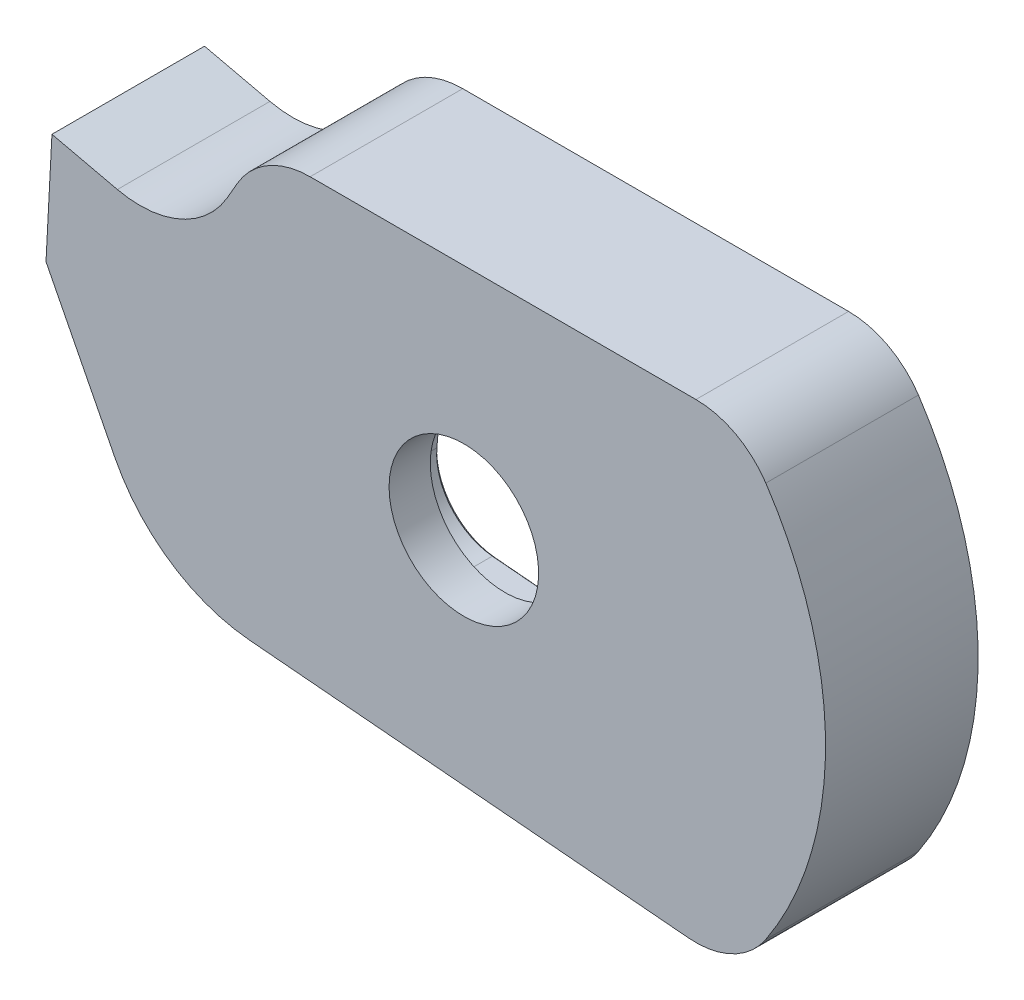
SolidWorks part; units mm, degrees
material "AISI 4340 Aço, normalizado"
ref_plane "Plano frontal" through (0, 0, 0) normal (0, 0, 1) x (1, 0, 0)
ref_plane "Plano superior" through (0, 0, 0) normal (0, 1, 0) x (1, 0, 0)
ref_plane "Plano direito" through (0, 0, 0) normal (1, 0, 0) x (0, 0, -1)
other "Center of Mass"
sketch "Sketch2" plane through (0, 0, 0) normal (0, 0, 1) x (1, 0, 0)
  line L0 (0, 0) -> (-50, 0) construction
  line L1 (-115.1603, 41.8011) -> (-136.5964, 46.75)
  line L2 (0, 0) -> (-142.97, 20.0931) construction
  line L5 (-51.9968, 77) -> (74.4153, 77)
  line L6 (0, 0) -> (0, 41.2714) construction
  line L8 (-75.8125, 63.25) -> (-79.158, 57.4553)
  line L14 (-71.7951, -64.424) -> (71.9488, -77)
  line L19 (-136.5964, 46.75) -> (-138.542, 9.625)
  line L20 (-137.1069, 44.5388) -> (-135.4014, 51.9262) construction
  line L22 (-138.542, 9.625) -> (-116.0069, -34.6028)
  circle A0 centre (0, 0) radius 144.375 construction
  arc A5 (74.4153, 77) -> (97.3123, 64.7308) centre (74.4153, 49.5) cw
  arc A6 (-51.9968, 77) -> (-75.8125, 63.25) centre (-51.9968, 49.5) ccw
  arc A17 (-116.0069, -34.6028) -> (-71.7951, -64.424) centre (-67.0015, -9.6333) ccw
  arc A18 (-115.1603, 41.8011) -> (-79.158, 57.4553) centre (-107.7369, 73.9553) ccw
  arc A20 (97.3123, 64.7308) -> (97.2212, -64.8676) centre (0, 0) cw
  arc A21 (71.9488, -77) -> (97.2212, -64.8676) centre (74.3456, -49.6046) ccw
  point P29 (-144.375, 0)
  point P31 (29.3939, 77)
  point P32 (-67.8739, 77)
  point P33 (97.3123, -64.7308)
  dimension "D1" = 288.75
  dimension "D4" = 27.5
  dimension "D5" = 33
  dimension "D13" = 27.5
  dimension "D11" = 55
  dimension "D10" = 77
  dimension "D2" = 5
  dimension "D3" = 10
  dimension "D7" = 30
  dimension "D8" = 77
  dimension "D12" = 30
  dimension "D9" = 46.75
  dimension "D14" = 37.125
  dimension "D15" = 22
  dimension "D6" = 27.5
  dimension "D16" = 5
  dimension "D17" = 77
extrude "EXTRUSÃO GEOMETRIA" add sketch "Sketch2" along normal blind 50 contours L5 A5 A20 A21 L14 A17 L22 L19 L1 A18 L8 A6
sketch "Esboço3"
  line L0 (119.5605, -25.8367) -> (117.6529, -4.0323)
  line L1 (125.3653, 6.5829) -> (138.542, 9.625)
  line L2 (138.542, 9.625) -> (116.0069, -34.6028) construction
  line L3 (138.542, 9.625) -> (116.0069, -34.6028)
  line L4 (71.7951, -64.424) -> (-71.9488, -77) construction
  line L5 (115.1603, 41.8011) -> (136.5964, 46.75) construction
  line L6 (31.1551, 77) -> (-22.8799, 20.2266)
  line L7 (51.9968, 77) -> (-74.4153, 77) construction
  line L8 (-28.0452, 17.3392) -> (-116.865, -1.5321)
  line L9 (31.1551, 77) -> (-74.4153, 77)
  arc A0 (71.7951, -64.424) -> (116.0069, -34.6028) centre (67.0015, -9.6333) ccw construction
  arc A1 (117.6529, -4.0323) -> (125.3653, 6.5829) centre (127.6148, -3.1608) cw
  arc A2 (119.5605, -25.8367) -> (116.0069, -34.6028) centre (67.0015, -9.6333) ccw
  arc A3 (-97.3123, 64.7308) -> (-97.2212, -64.8676) centre (0, 0) ccw construction
  arc A4 (-22.8799, 20.2266) -> (-28.0452, 17.3392) centre (-30.1235, 27.1209) cw
  arc A5 (-74.4153, 77) -> (-97.3123, 64.7308) centre (-74.4153, 49.5) ccw construction
  arc A6 (-97.3123, 64.7308) -> (-116.865, -1.5321) centre (0, 0) ccw
  arc A7 (-74.4153, 77) -> (-97.3123, 64.7308) centre (-74.4153, 49.5) ccw
  point P11 (-22.8799, 20.2266)
  point P24 (-36.8917, 15.4596)
  dimension "D1" = 10
  dimension "D3" = 10
  dimension "D2" = 22
sketch "Esboço3<3>" plane through (0, 0, 0) normal (0, 0, -1) x (-1, 0, 0) same geometry as "Esboço3"
other "Ponto de referência do centro da massa1"
ref_plane "Plano2" through (0, 1.9378, 0) normal (0, -1, 0) x (-1, 0, 0)
ref_plane "Plano3" through (-1.6368, 0, 0) normal (1, 0, 0) x (0, 0, -1)
sketch "Esboço2" plane through (0, 0, 0) normal (0, 0, -1) x (-1, 0, 0)
  line L0 (-8.25, 1.9378) -> (8.25, 1.9378) construction
  line L1 (-38.0236, 53.678) -> (31.7101, 59.7789)
  line L2 (-56.2044, 32.011) -> (-50.1035, -37.7226)
  line L3 (-28.4364, -55.9034) -> (41.2972, -49.8025)
  line L4 (53.3771, 41.5982) -> (59.478, -28.1355)
  line L5 (-57.9475, 51.9349) -> (61.2211, -48.0594) construction
  line L6 (-48.3603, -57.6465) -> (51.6339, 61.5221) construction
  line L7 (1.6368, 8.25) -> (1.6368, -8.25) construction
  line L8 (71.7951, -64.424) -> (-71.9488, -77) construction
  line L10 (2.503, 1.9378) -> (86.0271, 1.9378) construction
  circle A0 centre (1.6368, 1.9378) radius 24.5
  arc A2 (-38.0236, 53.678) -> (-56.2044, 32.011) centre (-36.2805, 33.7542) ccw
  arc A3 (31.7101, 59.7789) -> (53.3771, 41.5982) centre (33.4532, 39.8551) cw
  arc A4 (41.2972, -49.8025) -> (59.478, -28.1355) centre (39.5541, -29.8786) ccw
  arc A5 (-50.1035, -37.7226) -> (-28.4364, -55.9034) centre (-30.1796, -35.9795) ccw
  circle A6 centre (1.6368, 1.9378) radius 42.5
  dimension "D1" = 20
  dimension "D2" = 49
  dimension "D5" = 85
  dimension "D3" = 110
  dimension "D4" = 110
extrude "REBAIXO CAMISA" cut sketch "Esboço2" against normal blind 36.5 contours L1 A3 L4 A4 L3 A5 L2 A2
extrude "FURO EIXO" cut sketch "Esboço2<3>" against normal through all contours A0
sketch "Esboço2<3>" plane through (0, 0, 0) normal (0, 0, -1) x (-1, 0, 0) same geometry as "Esboço2"
chamfer "CHANFRO CAMISA" distance 1 angle 45 8 edges at (-6.4304, -52.8529, 0) (43.0353, -51.3004, 0) (-54.875, -42.7343, 0) (53.1539, -2.8558, 0) (-56.4275, 6.7314, 0) (51.6013, 46.6099, 0) (-46.3089, 55.1759, 0) (3.1568, 56.7285, 0)
sketch "REF. POLIA" plane through (0, 0, 0) normal (0, 0, -1) x (-1, 0, 0)
  circle A0 centre (1.6368, 1.9378) radius 75
  circle A1 centre (1.6368, 1.9378) radius 24.5 construction
  point P5 (0, 0)
  point P6 (10.688, 17.267)
  dimension "D1" = 150
equation "\"escala\" = 1                                            'projeto - escala geral"
equation "\"escala_disco-arma\"= 2.75                               'disco arma - escala geometria disco arma"
equation "\"rolamento_D-ext\"= 85                                   'rolamento arma - diametro externo"
equation "\"rolamento_d-int\"= 45                                   'rolamento arma - diametro interno"
equation "\"rolamento_b-esp\"= 23                                   'rolamento arma - espessura"
equation "\"arma_rebaixo-camisa_b\"= \"rolamento_b-esp\" + (\"arma-espessura\"-\"rolamento_b-esp\")/2        'disco arma - profundidade rebaixo camisa"
equation "\"arma-espessura\"= 50                                    'disco arma - espessura disco arma"
equation "\"D1@EXTRUSÃO GEOMETRIA\" = \"arma-espessura\""
equation "\"eixo_diam\"= \"rolamento_d-int\"                          'eixo arma - diametro"
equation "\"D2@Esboço2\" = \"eixo_diam\" + \"arma_eixo-furo_folga\""
equation "\"camisa_largura\"=110                                    'camisa arma - tamanho do lado"
equation "\"D3@Esboço2\"=\"camisa_largura\""
equation "\"camisa_raio\"=15                                        'camisa arma - raio canto interno"
equation "\"arma_rebaixo-camisa_raio\" = 5 + \"camisa_raio\"          'raio do rebaixo da camisa da arma "
equation "\"D1@Esboço2\"=\"arma_rebaixo-camisa_raio\""
equation "\"arma_alivio_raio\" = 12 * \"escala_disco-arma\""
equation "\"arma_diam_max\" = 105 * \"escala_disco-arma\""
equation "\"D1@Sketch2\" = \"arma_diam_max\""
equation "\"arma_arestas_raio\" = 10 * \"escala_disco-arma\""
equation "\"D4@Sketch2\" = \"arma_arestas_raio\""
equation "\"arma_altura_superior-centro\" = 28 * \"escala_disco-arma\""
equation "\"D10@Sketch2\" = \"arma_altura_superior-centro\""
equation "\"arma_dente_raio\" = 12 * \"escala_disco-arma\""
equation "\"D5@Sketch2\" = \"arma_dente_raio\""
equation "\"arma_altura_dente-centro\" = 17 * \"escala_disco-arma\""
equation "\"D9@Sketch2\"=\"arma_altura_dente-centro\""
equation "\"arma_dente_altura\" = 13.5 * \"escala_disco-arma\""
equation "\"arma_alivio-dente_raio\" = 20 * \"escala_disco-arma\""
equation "\"arma_traseira_offset\" = 10 * \"escala_disco-arma\""
equation "\"arma_centralizacao_offset\" = 8 * \"escala_disco-arma\""
equation "\"arma_eixo-furo_folga\" = 4                              'arma - folga entre furo arma e eixo"
equation "\"D1@REBAIXO CAMISA\" = \"arma_rebaixo-camisa_b\""
equation "\"D6@Sketch2\"=\"arma_traseira_offset\""
equation "\"D11@Sketch2\"=\"arma_alivio-dente_raio\""
equation "\"D4@Esboço2\"=\"camisa_largura\""
equation "\"D14@Sketch2\"=\"arma_dente_altura\""
equation "\"arma_altura_inferior-centro\" = 28 * \"escala_disco-arma\""
equation "\"D17@Sketch2\"=\"arma_altura_inferior-centro\""
equation "\"D13@Sketch2\"=\"arma_arestas_raio\""
equation "\"D5@Esboço2\"=\"rolamento_D-ext\""
equation "\"polia_diam_eff\" = 150 "
equation "\"D1@REF. POLIA\" = \"polia_diam_eff\""
equation "\"arma_dente_comprimento\"=22"
equation "\"D15@Sketch2\"=\"arma_dente_comprimento\""
